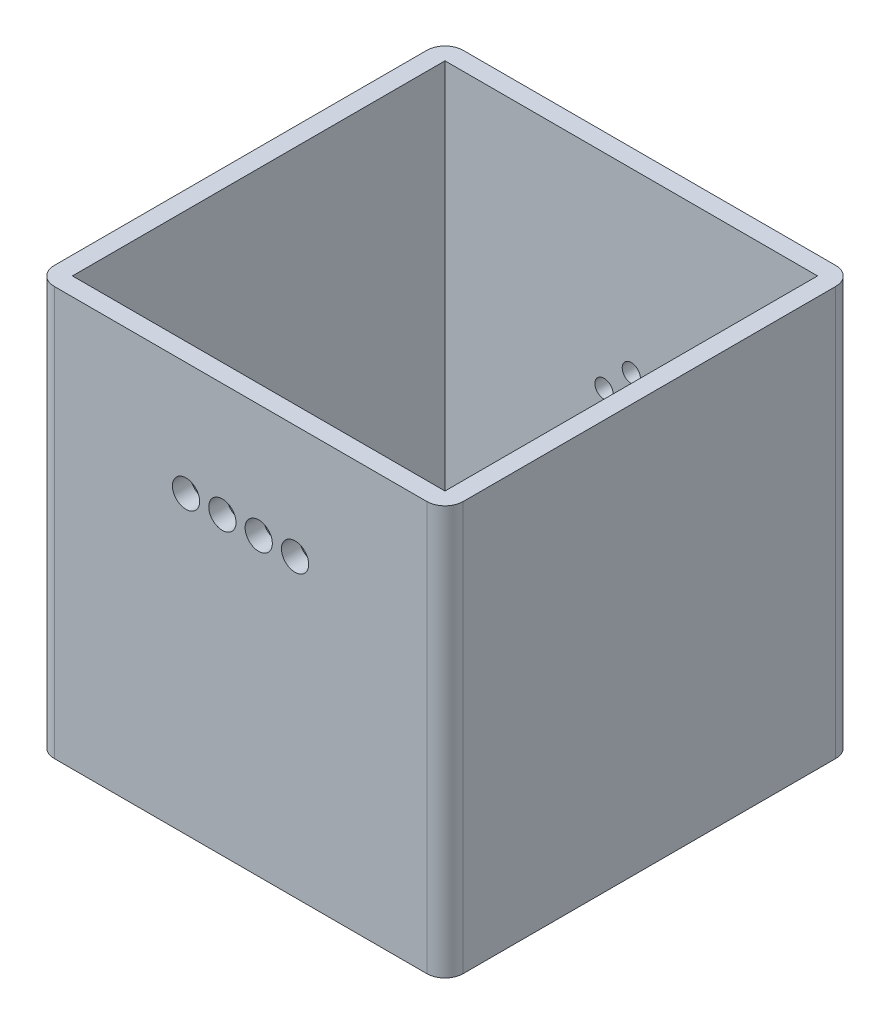
SolidWorks part; units mm, degrees
ref_plane "Front Plane" through (0, 0, 0) normal (0, 0, 1) x (1, 0, 0)
ref_plane "Top Plane" through (0, 0, 0) normal (0, 1, 0) x (1, 0, 0)
ref_plane "Right Plane" through (0, 0, 0) normal (1, 0, 0) x (0, 0, -1)
sketch "Sketch4" plane through (0, 0, 0) normal (0, 1, 0) x (1, 0, 0)
  line L1 (-22.5, 22.5) -> (22.5, 22.5)
  line L2 (-22.5, 22.5) -> (-22.5, -22.5)
  line L3 (-22.5, -22.5) -> (22.5, -22.5)
  line L4 (22.5, 22.5) -> (22.5, -22.5)
extrude "Boss-Extrude2" add sketch "Sketch4" along normal blind 22.5 and the other way blind 22.5
sketch "Sketch5" plane through (0, 0, 0) normal (0, 1, 0) x (1, 0, 0)
  line L1 (-20.5, 20.5) -> (20.5, 20.5)
  line L2 (-20.5, 20.5) -> (-20.5, -20.5)
  line L3 (-20.5, -20.5) -> (20.5, -20.5)
  line L4 (20.5, 20.5) -> (20.5, -20.5)
extrude "Cut-Extrude1" cut sketch "Sketch5" against normal blind 20.5 and the other way blind 22.5
sketch "Sketch6" plane through (0, 0, 0) normal (0, 0, 1) x (1, 0, 0)
  circle A0 centre (2, 10) radius 1.5
  circle A1 centre (6, 10) radius 1.5
  circle A2 centre (-2, 10) radius 1.5
  circle A3 centre (-6, 10) radius 1.5
  point P2 (0, 0)
  point P5 (0, 0)
  point P6 (7.0973, 10)
  point P9 (-2.4132, 10)
  point P12 (3.5328, 11.0996)
  point P13 (-6.3719, 9.8694)
  point P14 (0, 0)
  point P15 (0, 0)
  point P16 (0, 0)
  point P17 (0, 0)
extrude "Cut-Extrude2" cut sketch "Sketch6" along normal blind 32.5
sketch "Sketch8" plane through (0, 0, 0) normal (0, 0, 1) x (1, 0, 0)
  line L0 (0, -24.75) -> (0, 24.75) construction
  line L1 (24.75, 0) -> (-24.75, 0) construction
  circle A0 centre (0, 0) radius 1
  circle A1 centre (3, 0) radius 1
  circle A2 centre (0, 3) radius 1
  circle A3 centre (-3, 0) radius 1
  circle A4 centre (0, -3) radius 1
  point P4 (0, 0)
  point P11 (0, 2.6411)
  point P14 (-2.7787, 0)
  point P17 (0, 0)
  point P18 (0, -2.7571)
extrude "Cut-Extrude3" cut sketch "Sketch8" against normal blind 32.5
sketch "Sketch9" plane through (0, 0, 0) normal (0, 0, 1) x (1, 0, 0)
  line L1 (-3.75, -13) -> (3.75, -13)
  line L2 (-3.75, -13) -> (-3.75, -16.5)
  line L3 (-3.75, -16.5) -> (3.75, -16.5)
  line L4 (3.75, -13) -> (3.75, -16.5)
extrude "Cut-Extrude4" cut sketch "Sketch9" against normal blind 32.5
fillet "Fillet2" radius 1 4 edges at (-3.75, -16.5, -21.5) (3.75, -16.5, -21.5) (-3.75, -13, -21.5) (3.75, -13, -21.5)
fillet "Fillet3" radius 2 4 edges at (-22.5, 0, 22.5) (22.5, 0, -22.5) (22.5, 0, 22.5) (-22.5, 0, -22.5)
